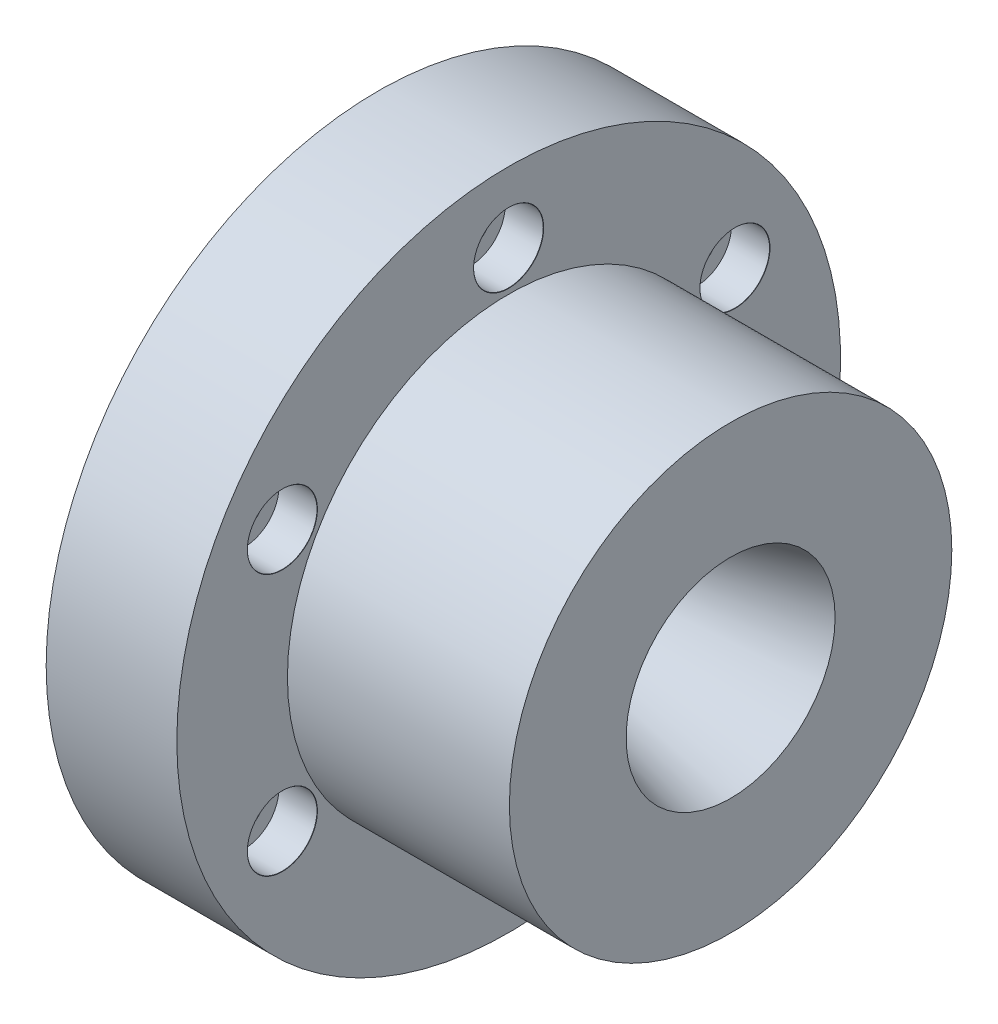
SolidWorks part; units mm, degrees
ref_plane "Front Plane" through (0, 0, 0) normal (0, 0, 1) x (1, 0, 0)
ref_plane "Top Plane" through (0, 0, 0) normal (0, 1, 0) x (1, 0, 0)
ref_plane "Right Plane" through (0, 0, 0) normal (1, 0, 0) x (0, 0, -1)
sketch "Sketch1" plane through (0, 0, 0) normal (0, 0, 1) x (1, 0, 0)
  line L2 (-20.1685, 17.5) -> (-2.6226, 7.3699)
  line L3 (1.1715, 6.8704) -> (20.3156, 12)
  line L4 (20.3156, 12) -> (20.3156, 25.4)
  line L5 (-20.1685, 17.5) -> (-20.1685, 25.4)
  line L6 (-20.1685, 25.4) -> (20.3156, 25.4)
  line L8 (0, 0) -> (-44.2999, 0) construction
  arc A0 (-2.6226, 7.3699) -> (1.1715, 6.8704) centre (-0.1226, 11.7) ccw
  dimension "D6" = 5
  dimension "D3" = 17.5
  dimension "D4" = 12
  dimension "D1" = 11.7
  dimension "D2" = 25.4
  dimension "D5" = 30
  dimension "D7" = 15
revolve "Revolve1" add sketch "Sketch1" angle 360 about L8
sketch "Sketch2" plane through (-20.1685, 0, 0) normal (-1, 0, 0) x (0, 0, 1)
  circle A0 centre (0, 0) radius 38.1
  circle A1 centre (0, 0) radius 25.4 construction
  circle A2 centre (0, 0) radius 25.4
  dimension "D1" = 76.2
extrude "Boss-Extrude1" add sketch "Sketch2" against normal blind 15
hole_wizard "CBORE for M4 Hex Socket Head Cap Screw1" positions "Sketch4" profile "Sketch6" counterbore size "M4" standard "ISO" end condition through all
sketch "Sketch4" plane through (-5.1685, 0, 0) normal (1, 0, 0) x (0, 0, -1)
  circle A1 centre (0, 0) radius 30 construction
  point P0 (0, 30)
  dimension "D1" = 60
sketch "Sketch6" plane through (-5.1685, 30, 0) normal (0, 1, 0) x (0, 0, -1)
  line L0 (0, 0) -> (0, 15)
  line L1 (0, 15) -> (2.25, 15)
  line L3 (2.25, 15) -> (2.25, 4.4)
  line L4 (4, 4.4) -> (2.25, 4.4)
  line L5 (4, 4.4) -> (4, 0.025)
  line L6 (4, 0.025) -> (4.025, 0)
  line L7 (4.025, 0) -> (0, 0)
  line L8 (-4, 0.025) -> (-4.025, 0) construction
  line L11 (0, -6.35) -> (0, 107.95) construction
  dimension "Thru Hole Dia." = 4.5
  dimension "Thru Hole Depth" = 15
  dimension "C'Bore Dia." = 8
  dimension "C'Bore Depth" = 4.4
  dimension "Near C'Sink Dia." = 8.05
  dimension "Near C'Sink Angle" = 90
pattern_circular "CirPattern1" count 6 over 360 about axis through (-5.1685, 0, 0) along (-1, 0, 0) of "CBORE for M4 Hex Socket Head Cap Screw1"
equation "\"D1@Sketch1\"= 13.4 / 2 + \"D6@Sketch1\""
